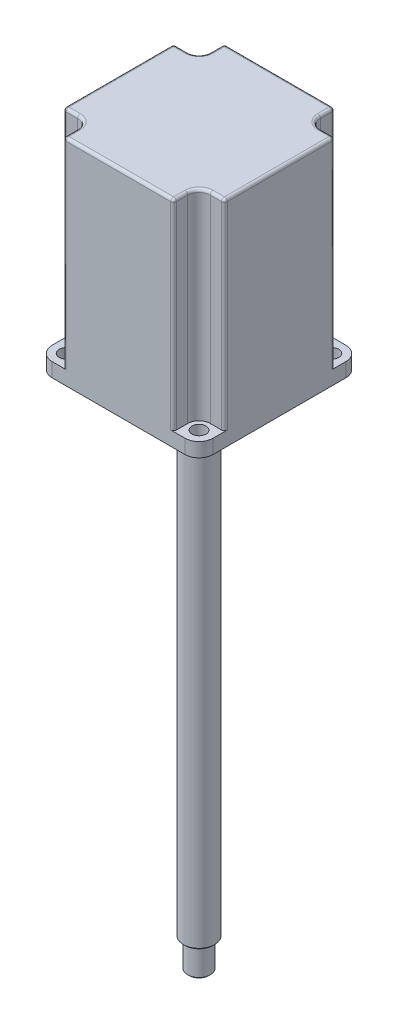
SolidWorks part; units mm, degrees
note: '?' marks a value the reader was unsure of.
material "1023 Carbon Steel Sheet (SS)"
ref_plane "Front" through (0, 0, 0) normal (0, 0, 1) x (1, 0, 0)
ref_plane "Top" through (0, 0, 0) normal (0, 1, 0) x (1, 0, 0)
ref_plane "Right" through (0, 0, 0) normal (1, 0, 0) x (0, 0, -1)
ref_axis "Axis1" through (-84.4107, 0, 0) along (1, 0, 0)?
ref_axis "Axis2" through (0, 64.3378, 0) along (0, -1, 0)?
ref_axis "Axis3" through (0, 0, -102.329) along (0, 0, 1)?
sketch "Sketch1" plane through (0, 0, 0) normal (0, 1, 0) x (1, 0, 0)
  line L1 (-28.5, -28.5) -> (28.5, -28.5)
  line L2 (-28.5, -28.5) -> (-28.5, 28.5)
  line L3 (-28.5, 28.5) -> (28.5, 28.5)
  line L4 (28.5, -28.5) -> (28.5, 28.5)
  line L5 (-28.5, -28.5) -> (28.5, 28.5) construction
  line L6 (-28.5, 28.5) -> (28.5, -28.5) construction
  point P0 (0, 0)
  dimension "D1" = 57
  dimension "D2" = 57
extrude "Extrude1" add sketch "Sketch1" along normal blind 76
hole_wizard "Ø5.0 (5) Diameter Hole1" positions "Sketch5" profile "Sketch4" hole size "Ø5.0" standard "ISO" end condition through all
sketch "Sketch5" plane through (0, 0, 0) normal (0, -1, 0) x (1, 0, 0)
  line L0 (-28.5, 28.5) -> (28.5, -28.5) construction
  line L3 (28.5, 28.5) -> (-28.5, -28.5) construction
  point P0 (-23.5, 23.5)
  point P1 (23.5, 23.5)
  point P3 (23.5, -23.5)
  point P5 (-23.5, -23.5)
  dimension "D1" = 47
  dimension "D2" = 47
sketch "Sketch4" plane through (-23.5, 0, 23.5) normal (1, 0, 0) x (0, 0, -1)
  line L0 (0, 0) -> (0, 76)
  line L1 (0, 76) -> (2.5, 76)
  line L2 (2.5, 76) -> (2.5, 0)
  line L5 (2.5, 0) -> (0, 0)
  line L11 (0, -6.35) -> (0, 107.95) construction
  dimension "Thru Hole Dia." = 5
  dimension "Thru Hole Depth" = 76
sketch "Sketch6" plane through (0, 76, 0) normal (0, 1, 0) x (1, 0, 0)
  line L0 (-19.5, 23.5) -> (-19.5, 32.5117)
  line L1 (-19.5, 32.5117) -> (-33.9089, 32.5117)
  line L2 (-33.9089, 32.5117) -> (-33.9089, 19.5)
  line L3 (-33.9089, 19.5) -> (-23.5, 19.5)
  line L4 (19.5, 23.5) -> (19.5, 36.4716)
  line L5 (19.5, 36.4716) -> (41.1684, 36.4716)
  line L6 (41.1684, 36.4716) -> (41.1684, 19.5)
  line L7 (41.1684, 19.5) -> (23.5, 19.5)
  line L8 (23.5, -19.5) -> (44.2522, -19.5)
  line L9 (44.2522, -19.5) -> (44.2522, -40.0504)
  line L10 (44.2522, -40.0504) -> (19.5, -40.0504)
  line L11 (19.5, -40.0504) -> (19.5, -23.5)
  line L12 (-23.5, -19.5) -> (-37.6708, -19.5)
  line L13 (-37.6708, -19.5) -> (-37.6708, -37.8282)
  line L14 (-37.6708, -37.8282) -> (-19.5, -37.8282)
  line L15 (-19.5, -37.8282) -> (-19.5, -23.5)
  circle A0 centre (-23.5, 23.5) radius 4
  circle A1 centre (23.5, 23.5) radius 4
  circle A2 centre (23.5, -23.5) radius 4
  circle A3 centre (-23.5, -23.5) radius 4
  circle M1 centre (-23.5, -23.5) radius 2.5
  circle M2 centre (23.5, -23.5) radius 2.5
  circle M3 centre (23.5, 23.5) radius 2.5
  circle M4 centre (-23.5, 23.5) radius 2.5
  line M5 (28.5, -28.5) -> (28.5, 28.5)
  line M6 (28.5, 28.5) -> (-28.5, 28.5)
  line M7 (-28.5, 28.5) -> (-28.5, -28.5)
  line M8 (-28.5, -28.5) -> (28.5, -28.5)
  dimension "D1" = 8
  dimension "D2" = 8
  dimension "D3" = 8
  dimension "D4" = 8
extrude "Extrude4" cut sketch "Sketch6" against normal blind 71 contours L2 L3 L0 L1 M7 M6 | A0 L0 L3 M6 M7 | A0 M4 | L7 L6 L5 L4 M6 M5 | A1 L7 L4 M5 M6 | A1 M3 | A2 M2 | A2 L11 L8 M8 M5 | L11 L10 L9 L8 M5 M8 | L14 L15 L12 L13 M8 M7 | A3 L12 L15 M7 M8 | A3 M1
fillet "Fillet1" radius 5 4 edges at (-28.5, 2.5, 28.5) (28.5, 2.5, 28.5) (28.5, 2.5, -28.5) (-28.5, 2.5, -28.5)
sketch "Sketch7" plane through (0, 76, 0) normal (0, 1, 0) x (1, 0, 0)
  circle A0 centre (0, 0) radius 3
  dimension "D1" = 6
extrude "Extrude5" add sketch "Sketch7" against normal blind 101 separate body
sketch "Sketch8" plane through (0, 0, 0) normal (0, -1, 0) x (1, 0, 0)
  circle A0 centre (0, 0) radius 15
  dimension "D1" = 30
extrude "Extrude6" add sketch "Sketch8" along normal blind 3
fillet "Fillet2" radius 1 24 edges at (-26, 76, 19.5) (-20.6716, 76, 20.6716) (-19.5, 76, 26) (0, 76, 28.5) (19.5, 76, 26) (20.6716, 76, 20.6716) (26, 76, 19.5) (28.5, 76, 0) (19.5, 76, -26) (26, 76, -19.5) (20.6716, 76, -20.6716) (-26, 76, -19.5) (-19.5, 76, -26) (-20.6716, 76, -20.6716) (0, 76, -28.5) (-28.5, 76, 0) (-19.5, 40.5, 28.5) (-28.5, 40.5, 19.5) (-28.5, 40.5, -19.5) (-19.5, 40.5, -28.5) (19.5, 40.5, -28.5) (28.5, 40.5, -19.5) (28.5, 40.5, 19.5) (19.5, 40.5, 28.5)
sketch "Sketch9" plane through (0, 0, 0) normal (0, -1, 0) x (1, 0, 0)
  circle A0 centre (0, 0) radius 5.5
  dimension "D1" = 11
extrude "Boss-Extrude1" add sketch "Sketch9" along normal blind 174
chamfer "Chamfer1" distance 0.5 angle 45 1 edges at (0, -174, -5.5)
sketch "Sketch10" plane through (0, -174, 0) normal (0, -1, 0) x (1, 0, 0)
  circle A0 centre (0, 0) radius 4
  dimension "D1" = 8
extrude "Boss-Extrude2" add sketch "Sketch10" along normal blind 10
chamfer "Chamfer2" distance 0.5 angle 45 1 edges at (0, -184, -4)
